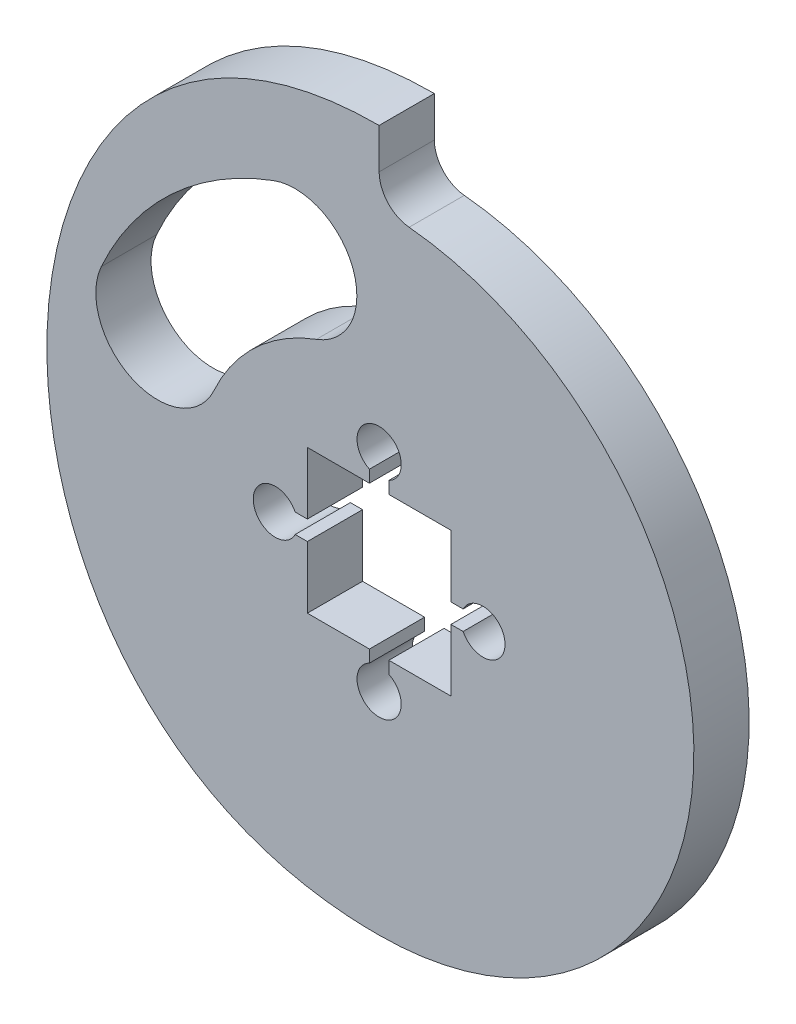
SolidWorks part; units mm, degrees
material "AISI 1020 Steel, Cold Rolled"
ref_plane "Front Plane" through (0, 0, 0) normal (0, 0, 1) x (1, 0, 0)
ref_plane "Top Plane" through (0, 0, 0) normal (0, 1, 0) x (1, 0, 0)
ref_plane "Right Plane" through (0, 0, 0) normal (1, 0, 0) x (0, 0, -1)
sketch "Sketch1" plane through (0, 0, 0) normal (0, 0, 1) x (1, 0, 0)
  line L0 (1.1176, -8.255) -> (8.255, -8.255)
  line L1 (-8.255, 8.255) -> (-1.1176, 8.255)
  line L2 (-8.255, 8.255) -> (-8.255, 1.1176)
  line L3 (-8.255, -8.255) -> (-1.1176, -8.255)
  line L4 (8.255, 8.255) -> (8.255, 1.1176)
  line L5 (8.255, -1.1176) -> (8.255, -8.255)
  line L6 (1.1176, 8.255) -> (8.255, 8.255)
  line L7 (8.255, 8.255) -> (-8.255, -8.255) construction
  line L9 (-9.6571, 1.1176) -> (-8.255, 1.1176)
  line L11 (-9.6571, -1.1176) -> (-8.255, -1.1176)
  line L14 (-1.1176, 9.6571) -> (-1.1176, 8.255)
  line L16 (1.1176, 9.6571) -> (1.1176, 8.255)
  line L25 (0, 0) -> (11.938, 0) construction
  line L27 (-8.255, -1.1176) -> (-8.255, -8.255)
  line L28 (0, 44.45) -> (0, 36.195)
  line L45 (-1.1176, -8.255) -> (-1.1176, -9.6571)
  line L47 (1.1176, -8.255) -> (1.1176, -9.6571)
  line L48 (8.255, -1.1176) -> (9.6571, -1.1176)
  line L50 (8.255, 1.1176) -> (9.6571, 1.1176)
  arc A2 (-1.1176, -9.6571) -> (1.1176, -9.6571) centre (0, -11.938) ccw
  arc A3 (9.6571, -1.1176) -> (9.6571, 1.1176) centre (11.938, 0) ccw
  arc A31 (-9.6571, 1.1176) -> (-9.6571, -1.1176) centre (-11.938, 0) ccw
  arc A32 (1.1176, 9.6571) -> (-1.1176, 9.6571) centre (0, 11.938) ccw
  arc A41 (0, -36.195) -> (0, 36.195) centre (0, 0) ccw
  spline S0 degree 3 poles (0, 44.45) (-26.6002, 44.45) (-51.0523, 0.651) (-24.1552, -36.3491) (0, -36.195) knots 0 0 0 0 0.529165 1 1 1 1
  point P1 (0, 0)
  dimension "D2" = 11.938
  dimension "D4" = 5.08
  dimension "D6" = 16.51
  dimension "D7" = 38.1
  dimension "D14" = 72.39
  dimension "D3" = 44.45
  dimension "D1" = 16.51
  dimension "D5" = 2.2352
extrude "Boss-Extrude1" add sketch "Sketch1" along normal blind 6.35 contours A32 L16 L6 L4 L50 A3 L48 L5 L0 L47 A2 L45 L3 L27 L11 A31 L9 L2 L1 L14 region at (-1.0973, 40.3225, 0)
sketch "Sketch5" plane through (0, 0, 6.35) normal (0, 0, 1) x (1, 0, 0)
  arc A0 (-25.4675, 11.4914) -> (-9.6739, 26.2118) centre (0, 0) cw construction
  arc A1 (-12.1364, 32.8839) -> (-31.9501, 14.4164) centre (0, 0) ccw
  arc A2 (-7.2115, 19.5397) -> (-18.9848, 8.5663) centre (0, 0) ccw
  arc A3 (-7.2115, 19.5397) -> (-12.1364, 32.8839) centre (-9.6739, 26.2118) ccw
  arc A4 (-31.9501, 14.4164) -> (-18.9848, 8.5663) centre (-25.4675, 11.4914) ccw
  point P4 (-19.05, 20.4387)
  dimension "D1" = 27.94
  dimension "D2" = 7.112
  dimension "D3" = 21.59
  dimension "D4" = 19.05
extrude "Cut-Extrude1" cut sketch "Sketch5" against normal through all
fillet "Fillet2" radius 3.81 1 edges at (0, 36.195, 3.175)
